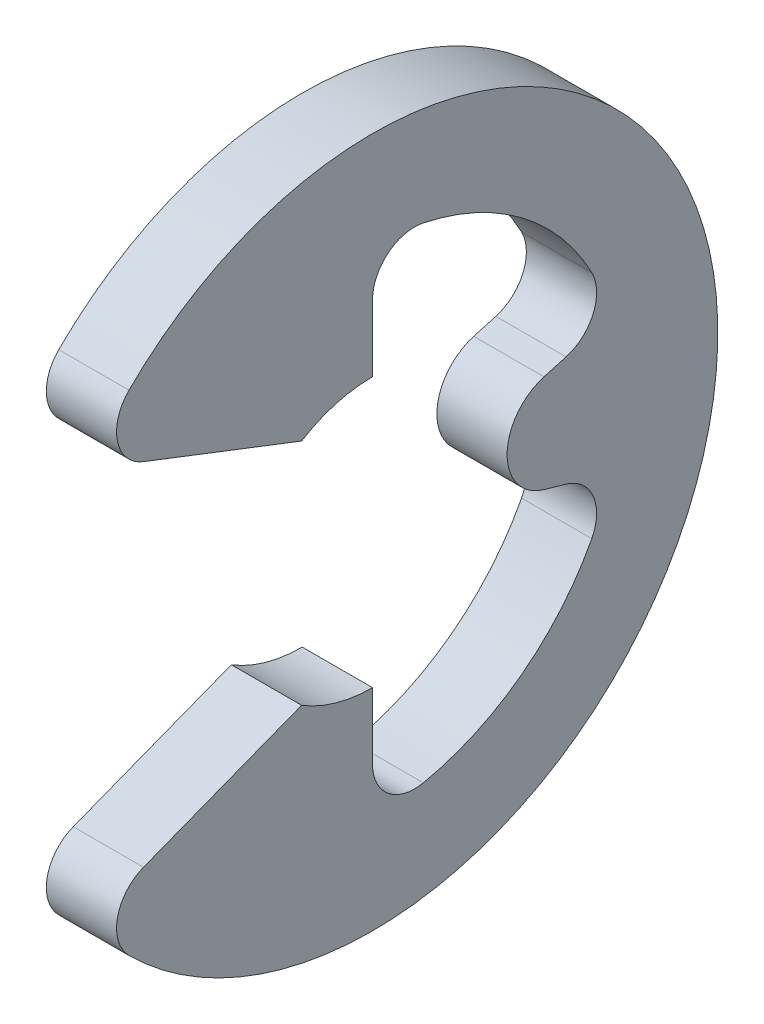
SolidWorks part; units mm, degrees
note: '?' marks a value the reader was unsure of.
other "Imported1" parameters "D1"=0.36, "D2"=1.7342, "Ring Thickness"=0.6, "Groove Width"=0.64, "OD"=95.4673, "L2"=3.25, "Df"=44.9367, "Dg"=1.2, "D5"=1.1938, "G"=2.9, "D3"=8.0325, "D4"=4.6385, "A"=1.01, "Ring OD"=19.0132, "Groove Diameter"=9.0385
ref_plane "Front" through (0, 0, 0) normal (0, 0, 1) x (1, 0, 0)
ref_plane "Top" through (0, 0, 0) normal (0, 1, 0) x (1, 0, 0)
ref_plane "Right" through (0, 0, 0) normal (1, 0, 0) x (0, 0, -1)
sketch "Sketch2" plane through (0, 0, 0) normal (1, 0, 0) x (0, 0, -1)
  circle A0 centre (0, 0) radius 2.95 construction
  circle A1 centre (0, 0) radius 1.15 construction
  dimension "Ring OD" = 5.9
sketch "Sketch3" plane through (0, 0, 0) normal (0, 1, 0) x (1, 0, 0)
  line L0 (0.3, 2.95) -> (-0.3, 2.95) construction
  line L1 (-0.32, -2.065) -> (0.32, -2.065) construction
  line L3 (0, -2.95) -> (0, 2.95) construction
  line L4 (0, -2.95) -> (0, 2.95) construction
  point P4 (0, -2.065)
  point P6 (0, 2.95)
  dimension "D1" = 1.77
sketch "Sketch1" plane through (0, 0, 0) normal (1, 0, 0) x (0, 0, -1)
  line L0 (-2.424, -1.6812) -> (-0.6058, -0.9775)
  line L1 (-2.424, 1.6812) -> (-0.6058, 0.9775)
  line L2 (0, -1.15) -> (0, -2.1161)
  line L3 (0, 1.15) -> (0, 2.1161)
  line L4 (1.106, -0.3149) -> (2.0352, -0.5795)
  line L5 (1.106, 0.3149) -> (2.0352, 0.5795)
  line L6 (0, 0) -> (-1.625, 0) construction
  line L7 (1.106, 0.3149) -> (1.106, -0.3149) construction
  line L8 (-0.6058, 0.9775) -> (0, 1.15) construction
  line L9 (-0.6058, -0.9775) -> (0, -1.15) construction
  circle A1 centre (0, 0) radius 2.95 construction
  circle A2 centre (0, 0) radius 1.15 construction
  arc A3 (-2.424, -1.6812) -> (-2.424, 1.6812) centre (0, 0) ccw
  arc A4 (-0.6058, 0.9775) -> (0, 1.15) centre (0, 0) cw
  arc A5 (-0.6058, -0.9775) -> (0, -1.15) centre (0, 0) ccw
  arc A6 (1.106, 0.3149) -> (1.106, -0.3149) centre (0, 0) cw
  arc A7 (0, -2.1161) -> (2.0352, -0.5795) centre (0, 0) ccw
  arc A8 (2.0352, 0.5795) -> (0, 2.1161) centre (0, 0) ccw
  circle A9 centre (0, 0) radius 1.15 construction
  point P12 (1.106, 0)
  dimension "D1" = 2.1161
  dimension "D2" = 1.3859
  dimension "D3" = 1.955
extrude "Extrude1" add sketch "Sketch1" along normal mid plane 0.6
fillet "Fillet1" radius 0.36 6 edges at (0, -2.1161, 0) (0, 2.1161, 0) (0, -1.6812, 2.424) (0, 1.6812, 2.424) (0, -0.5795, -2.0352) (0, 0.5795, -2.0352)
sketch "Sketch4" plane through (0, 0, 0) normal (1, 0, 0) x (0, 0, -1)
  line L0 (-2.95, 0) -> (2.95, 0) construction
  line L5 (1.6531, 0.4707) -> (1.106, 0.3149) construction
  line L6 (1.106, -0.3149) -> (1.6531, -0.4707) construction
  line L7 (1.106, -0.3149) -> (1.4649, -0.4171)
  line L8 (1.4649, 0.4171) -> (1.106, 0.3149)
  arc A4 (1.4649, 0.4171) -> (1.4649, -0.4171) centre (1.5837, 0) ccw
  circle A5 centre (0, 0) radius 1.15 construction
  arc A6 (1.106, -0.3149) -> (1.106, 0.3149) centre (0, 0) ccw
extrude "Cut-Extrude1" cut sketch "Sketch4" against normal through all both and the other way through all contours A6 A4 L8 | A6 L7 A4
ref_plane "Contact Plane 1" through (0.3, 0, 0) normal (1, 0, 0) x (0, 0, -1)
ref_plane "Contact Plane 2" through (-0.3, 0, 0) normal (-1, 0, 0) x (0, 0, 1)
ref_axis "Center Axis 1" through (5.5343, 0, 0) along (-1, 0, 0)?
equation "\"D1@Fillet1\" = \"Ring Thickness@Sketch3\" * .6"
equation "\"D1@Sketch1\" = ( \"Ring OD@Sketch2\" + \"Groove Diameter@Sketch2\" ) / 3.875"
equation "\"D1@Sketch3\"=\"Ring OD@Sketch2\"*.3"
equation "\"D3@Sketch1\"=\"Groove Diameter@Sketch2\"*.85"
